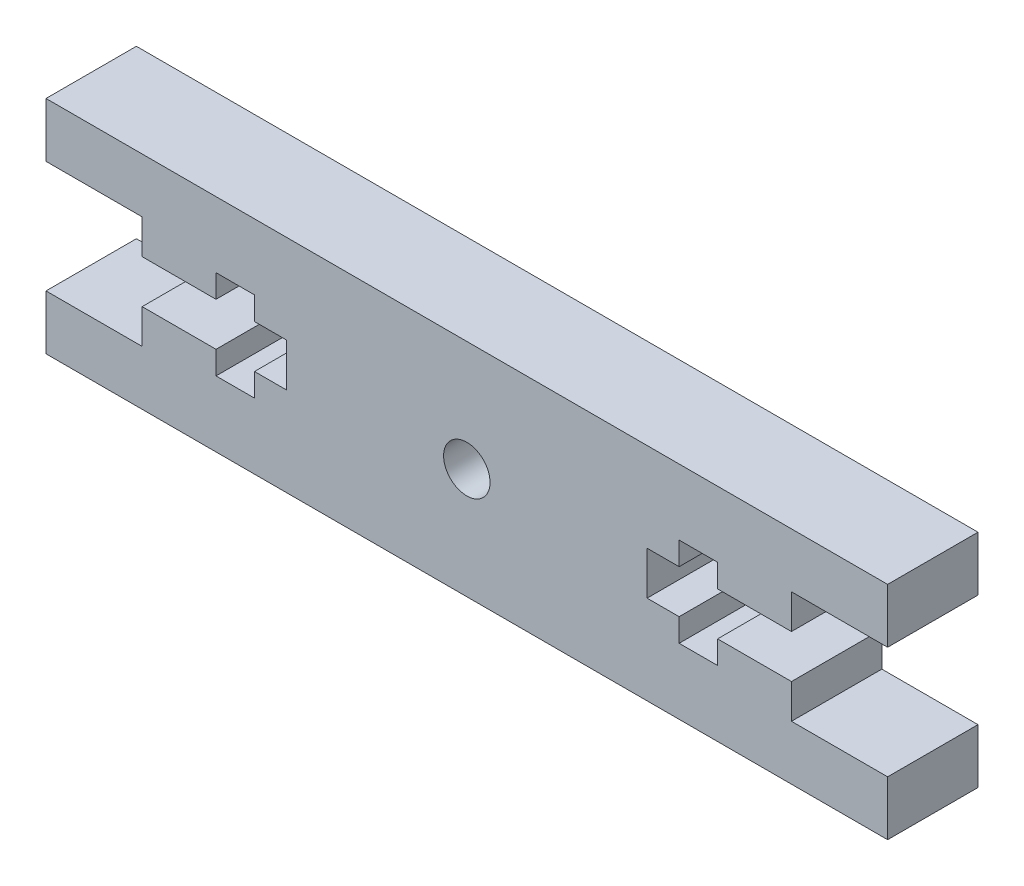
SolidWorks part; units mm, degrees
material "Acrylic (Medium-high impact)"
ref_plane "Front Plane" through (0, 0, 0) normal (0, 0, 1) x (1, 0, 0)
ref_plane "Top Plane" through (0, 0, 0) normal (0, 1, 0) x (1, 0, 0)
ref_plane "Right Plane" through (0, 0, 0) normal (1, 0, 0) x (0, 0, -1)
sketch "Sketch1" plane through (0, 0, 0) normal (0, 0, 1) x (1, 0, 0)
  line L0 (727.3294, 349.1985) -> (779.8494, 349.1985)
  line L1 (753.5894, -654.3154) -> (753.5894, 49345.6846) construction
  line L2 (742.3394, 343.6485) -> (742.3394, 340.9485)
  line L3 (727.3294, 345.7985) -> (733.3294, 345.7985)
  line L4 (733.3294, 345.7985) -> (733.3294, 343.6485)
  line L5 (733.3294, 343.6485) -> (737.9394, 343.6485)
  line L6 (737.9394, 345.0885) -> (740.3394, 345.0885)
  line L7 (-245.8122, 342.2985) -> (49754.1878, 342.2985) construction
  line L8 (727.3294, 335.3985) -> (727.3294, 338.7985)
  line L9 (737.9394, 340.9485) -> (737.9394, 339.5085)
  line L10 (740.3394, 339.5085) -> (740.3394, 340.9485)
  line L11 (740.3394, 340.9485) -> (742.3394, 340.9485)
  line L12 (737.9394, 339.5085) -> (740.3394, 339.5085)
  line L13 (733.3294, 340.9485) -> (737.9394, 340.9485)
  line L14 (740.3394, 343.6485) -> (742.3394, 343.6485)
  line L15 (740.3394, 345.0885) -> (740.3394, 343.6485)
  line L16 (733.3294, 338.7985) -> (733.3294, 340.9485)
  line L17 (737.9394, 343.6485) -> (737.9394, 345.0885)
  line L18 (727.3294, 338.7985) -> (733.3294, 338.7985)
  line L19 (727.3294, 335.3985) -> (779.8494, 335.3985)
  line L20 (779.8494, 349.1985) -> (779.8494, 345.7985)
  line L21 (779.8494, 338.7985) -> (773.8494, 338.7985)
  line L22 (769.2394, 343.6485) -> (769.2394, 345.0885)
  line L23 (773.8494, 338.7985) -> (773.8494, 340.9485)
  line L24 (766.8394, 345.0885) -> (766.8394, 343.6485)
  line L25 (766.8394, 343.6485) -> (764.8394, 343.6485)
  line L26 (773.8494, 340.9485) -> (769.2394, 340.9485)
  line L27 (769.2394, 339.5085) -> (766.8394, 339.5085)
  line L28 (766.8394, 340.9485) -> (764.8394, 340.9485)
  line L29 (766.8394, 339.5085) -> (766.8394, 340.9485)
  line L30 (769.2394, 340.9485) -> (769.2394, 339.5085)
  line L31 (779.8494, 335.3985) -> (779.8494, 338.7985)
  line L32 (769.2394, 345.0885) -> (766.8394, 345.0885)
  line L33 (773.8494, 343.6485) -> (769.2394, 343.6485)
  line L34 (727.3294, 349.1985) -> (727.3294, 345.7985)
  line L35 (773.8494, 345.7985) -> (773.8494, 343.6485)
  line L36 (779.8494, 345.7985) -> (773.8494, 345.7985)
  line L37 (764.8394, 343.6485) -> (764.8394, 340.9485)
  circle A0 centre (753.5894, 342.2985) radius 1.45
  point P7 (753.5894, 349.1985)
  point P8 (764.8394, 342.2985)
  point P24 (742.3394, 342.2985)
  point P28 (753.5894, 335.3985)
  point P46 (753.5894, 349.1985)
  dimension "D10" = 2.9
  dimension "D1" = 3.4
  dimension "D3" = 6
  dimension "D4" = 1.44
  dimension "D5" = 2.4
  dimension "D9" = 2.7
  dimension "D2" = 7
  dimension "D6" = 7
  dimension "D7" = 20.26
extrude "Boss-Extrude2" add sketch "Sketch1" along normal blind 5.64
equation "\"D7@Sketch1\"=\"Hip_top_half_width@Hip_top_side-1.Part\""
